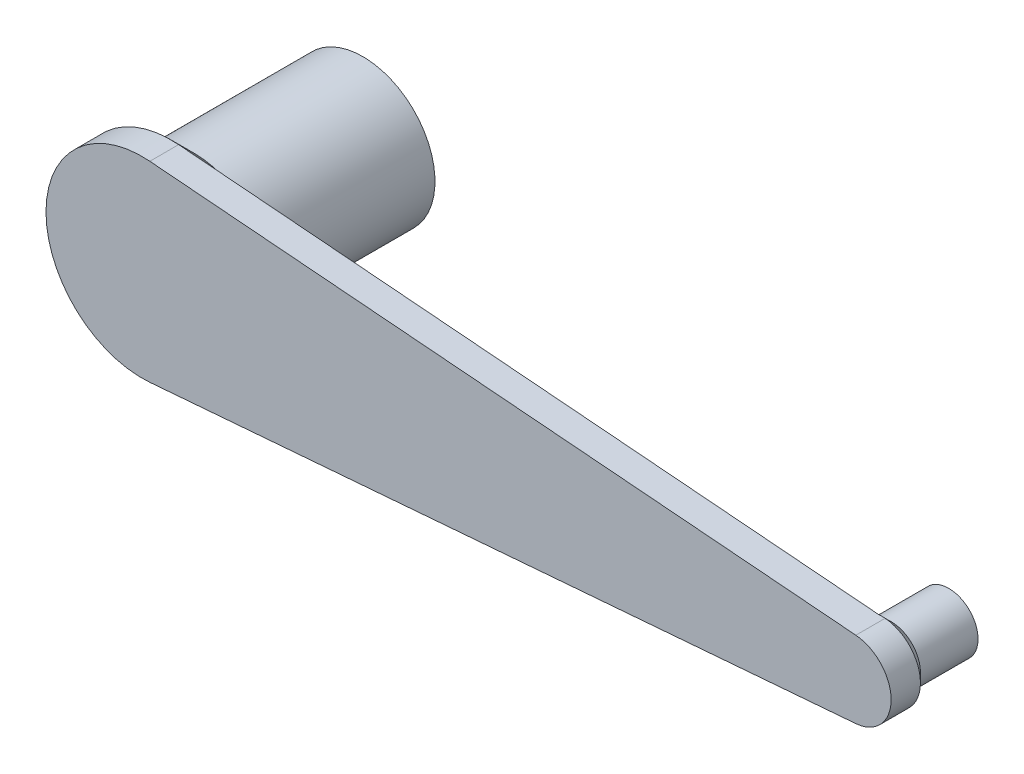
SolidWorks part; units mm, degrees
material "ABS"
ref_plane "Front Plane" through (0, 0, 0) normal (0, 0, 1) x (1, 0, 0)
ref_plane "Top Plane" through (0, 0, 0) normal (0, 1, 0) x (1, 0, 0)
ref_plane "Right Plane" through (0, 0, 0) normal (1, 0, 0) x (0, 0, -1)
sketch "Sketch1" plane through (0, 0, 0) normal (0, 0, 1) x (1, 0, 0)
  line L0 (0.8108, 9.9671) -> (74.3243, 3.9868)
  line L1 (74.3243, -3.9868) -> (0.8108, -9.9671)
  arc A0 (0.8108, -9.9671) -> (0.8108, 9.9671) centre (0, 0) cw
  arc A1 (74.3243, 3.9868) -> (74.3243, -3.9868) centre (74, 0) cw
  dimension "D1" = 4
  dimension "D2" = 10
  dimension "D3" = 74
extrude "Boss-Extrude1" add sketch "Sketch1" along normal blind 3
sketch "Sketch2" plane through (0, 0, 0) normal (0, 0, -1) x (-1, 0, 0)
  circle A0 centre (-74, 0) radius 3.05
  arc A1 (-74.3243, 3.9868) -> (-74.3243, -3.9868) centre (-74, 0) ccw construction
  dimension "D1" = 6.1
extrude "Boss-Extrude2" add sketch "Sketch2" along normal blind 7
chamfer "Chamfer1" distance 1 angle 45 1 edges at (70.95, 0, 0)
sketch "Sketch3" plane through (0, 0, 0) normal (0, 0, -1) x (-1, 0, 0)
  circle A0 centre (0, 0) radius 7.5
  dimension "D1" = 15
extrude "Boss-Extrude3" add sketch "Sketch3" along normal blind 20
chamfer "Chamfer2" distance 2.5 angle 45 1 edges at (-7.5, 0, 0)
